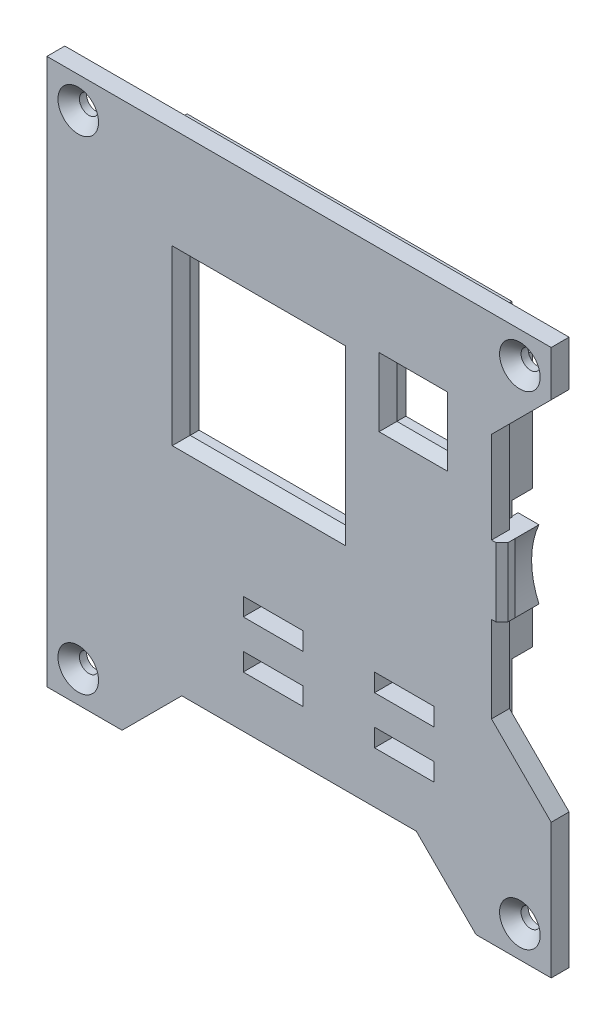
SolidWorks part; units mm, degrees
ref_plane "Front Plane" through (0, 0, 0) normal (0, 0, 1) x (1, 0, 0)
ref_plane "Top Plane" through (0, 0, 0) normal (0, 1, 0) x (1, 0, 0)
ref_plane "Right Plane" through (0, 0, 0) normal (1, 0, 0) x (0, 0, -1)
sketch "Sketch1" plane through (0, 0, 0) normal (0, 0, 1) x (1, 0, 0)
  line L0 (0.0172, 91.4623) -> (84.5172, 91.4623)
  line L1 (84.5172, 91.4623) -> (84.5172, 83.8623)
  line L2 (84.5172, 83.8623) -> (74.5172, 73.8623)
  line L3 (74.5172, 73.8623) -> (74.5172, 32.5623)
  line L4 (74.5172, 32.5623) -> (84.5172, 22.5623)
  line L5 (84.5172, 22.5623) -> (84.5172, -0.0377)
  line L6 (84.5172, -0.0377) -> (71.9172, -0.0377)
  line L7 (71.9172, -0.0377) -> (61.9172, 9.9623)
  line L8 (61.9172, 9.9623) -> (22.6172, 9.9623)
  line L9 (22.6172, 9.9623) -> (12.6172, -0.0377)
  line L10 (12.6172, -0.0377) -> (0.0172, -0.0377)
  line L11 (0.0172, -0.0377) -> (0.0172, 91.4623)
  dimension "D1" = 91.5
  dimension "D2" = 84.5
  dimension "D3" = 7.6
  dimension "D4" = 22.6
  dimension "D5" = 12.6
  dimension "D6" = 12.6
  dimension "D7" = 135
  dimension "D8" = 10
  dimension "D9" = 10
  dimension "D10" = 84.5
  dimension "D11" = 91.5
extrude "Boss-Extrude1" add sketch "Sketch1" along normal blind 3
sketch "Sketch3" plane through (0, 0, 3) normal (0, 0, 1) x (1, 0, 0)
  line L0 (84.5172, 91.4623) -> (0.0172, 91.4623) construction
  line L1 (5.2672, 86.2123) -> (79.2672, 86.2123) construction
  line L2 (5.2672, 86.2123) -> (5.2672, 5.2123) construction
  line L3 (5.2672, 5.2123) -> (79.2672, 5.2123) construction
  line L4 (79.2672, 86.2123) -> (79.2672, 5.2123) construction
  line L5 (5.2672, 86.2123) -> (79.2672, 5.2123) construction
  line L6 (5.2672, 5.2123) -> (79.2672, 86.2123) construction
  line L7 (0.0172, 91.4623) -> (0.0172, -0.0377) construction
  circle A0 centre (5.2672, 86.2123) radius 1.6
  circle A1 centre (79.2672, 86.2123) radius 1.6
  circle A2 centre (5.2672, 5.2123) radius 1.6
  circle A3 centre (79.2672, 5.2123) radius 1.6
  point P4 (42.2672, 45.7123)
  point P7 (42.2672, 91.4623)
  point P8 (42.2672, 86.2123)
  point P11 (0.0172, 45.7123)
  point P12 (5.2672, 45.7123)
  dimension "D3" = 3.2
  dimension "D4" = 3.2
  dimension "D5" = 3.2
  dimension "D6" = 3.2
  dimension "D1" = 74
  dimension "D2" = 81
extrude "Cut-Extrude1" cut sketch "Sketch3" against normal blind 3
chamfer "Chamfer1" distance 1.8 angle 45 4 edges at (6.8672, 5.2123, 3) (80.8672, 5.2123, 3) (80.8672, 86.2123, 3) (6.8672, 86.2123, 3)
sketch "Sketch5" plane through (0, 0, 3) normal (0, 0, 1) x (1, 0, 0)
  line L1 (22.5172, 72.9623) -> (48.5172, 72.9623)
  line L2 (22.5172, 72.9623) -> (22.5172, 46.9623)
  line L3 (22.5172, 46.9623) -> (48.5172, 46.9623)
  line L4 (48.5172, 72.9623) -> (48.5172, 46.9623)
  line L5 (57.1672, 74.8123) -> (65.6672, 74.8123)
  line L6 (57.1672, 74.8123) -> (57.1672, 66.3123)
  line L7 (57.1672, 66.3123) -> (65.6672, 66.3123)
  line L8 (65.6672, 74.8123) -> (65.6672, 66.3123)
  line L11 (84.5172, 91.4623) -> (0.0172, 91.4623) construction
  line L12 (0.0172, 91.4623) -> (0.0172, -0.0377) construction
  point P4 (29.4474, 52.8079)
  point P9 (65.6672, 70.5623)
  point P12 (61.4172, 74.8123)
  point P15 (35.5172, 72.9623)
  point P16 (22.5172, 59.9623)
  dimension "D1" = 8.5
  dimension "D2" = 8.5
  dimension "D3" = 26
  dimension "D4" = 26
  dimension "D5" = 20.9
  dimension "D6" = 61.4
  dimension "D7" = 35.5
  dimension "D8" = 31.5
extrude "Cut-Extrude2" cut sketch "Sketch5" against normal blind 3
chamfer "Chamfer2" distance 1.5 angle 45 8 edges at (48.5172, 59.9623, 3) (35.5172, 72.9623, 3) (22.5172, 59.9623, 3) (35.5172, 46.9623, 3) (61.4172, 66.3123, 3) (57.1672, 70.5623, 3) (61.4172, 74.8123, 3) (65.6672, 70.5623, 3)
sketch "Sketch7" plane through (0, 0, 3) normal (0, 0, 1) x (1, 0, 0)
  line L1 (72.7672, 58.5123) -> (76.2672, 58.5123)
  line L2 (72.7672, 58.5123) -> (72.7672, 47.0123)
  line L3 (72.7672, 47.0123) -> (76.2672, 47.0123)
  line L4 (76.2672, 58.5123) -> (76.2672, 47.0123)
  line L7 (74.5172, 32.5623) -> (74.5172, 73.8623) construction
  line L8 (84.5172, 91.4623) -> (0.0172, 91.4623) construction
  point P4 (76.2672, 52.7623)
  point P6 (74.5172, 58.5123)
  dimension "D1" = 38.7
  dimension "D2" = 11.5
  dimension "D3" = 3.5
extrude "Boss-Extrude3" add sketch "Sketch7" against normal blind 6.2
sketch "Sketch8" plane through (0, 0, -3.2) normal (0, 0, -1) x (-1, 0, 0)
  line L0 (-76.2672, 58.5123) -> (-76.2672, 47.0123)
  arc A0 (-76.2672, 58.5123) -> (-76.2672, 47.0123) centre (-89.0626, 52.7623) cw
extrude "Cut-Extrude3" cut sketch "Sketch8" against normal blind 3 and the other way through all
chamfer "Chamfer3" distance 1 angle 45 1 edges at (76.2672, 52.7623, -0.2)
sketch "Sketch9" plane through (0, 0, 0) normal (0, 0, -1) x (-1, 0, 0)
  line L0 (-48.5172, 46.9623) -> (-48.5172, 72.9623) construction
  line L1 (-48.0172, 39.9623) -> (-23.0172, 39.9623)
  line L2 (-48.0172, 39.9623) -> (-48.0172, 35.9623)
  line L3 (-48.0172, 35.9623) -> (-23.0172, 35.9623)
  line L4 (-23.0172, 39.9623) -> (-23.0172, 35.9623)
  line L5 (-46.5172, 74.9623) -> (-50.5172, 74.9623)
  line L6 (-46.5172, 74.9623) -> (-46.5172, 79.9623)
  line L7 (-46.5172, 79.9623) -> (-50.5172, 79.9623)
  line L8 (-50.5172, 74.9623) -> (-50.5172, 79.9623)
  line L9 (-24.5172, 74.9623) -> (-20.5172, 74.9623)
  line L10 (-24.5172, 74.9623) -> (-24.5172, 79.9623)
  line L11 (-24.5172, 79.9623) -> (-20.5172, 79.9623)
  line L12 (-20.5172, 74.9623) -> (-20.5172, 79.9623)
  line L13 (-22.5172, 72.9623) -> (-22.5172, 46.9623) construction
  line L14 (-48.5172, 72.9623) -> (-22.5172, 72.9623) construction
  line L15 (-22.5172, 46.9623) -> (-48.5172, 46.9623) construction
  dimension "D1" = 2
  dimension "D2" = 2
  dimension "D3" = 2
  dimension "D4" = 2
  dimension "D5" = 5
  dimension "D6" = 5
  dimension "D7" = 4
  dimension "D8" = 4
  dimension "D9" = 7
  dimension "D10" = 4
extrude "Boss-Extrude4" add sketch "Sketch9" along normal blind 1.9
sketch "Sketch10" plane through (0, 0, 0) normal (0, 0, -1) x (-1, 0, 0)
  line L0 (-84.5172, 91.4623) -> (-0.0172, 91.4623) construction
  line L1 (-21.4172, 80.9623) -> (-72.9172, 80.9623)
  line L2 (-21.4172, 80.9623) -> (-21.4172, 77.9623)
  line L3 (-21.4172, 77.9623) -> (-69.5172, 77.9623)
  line L6 (-72.9172, 80.9623) -> (-72.9172, 60.9623)
  line L7 (-72.9172, 60.9623) -> (-69.5172, 60.9623)
  line L8 (-69.5172, 77.9623) -> (-69.5172, 60.9623)
  line L9 (-72.9172, 44.4243) -> (-69.5172, 44.4243)
  line L10 (-72.9172, 44.4243) -> (-72.9172, 37.9623)
  line L12 (-69.5172, 44.4243) -> (-69.5172, 40.9623)
  line L13 (-52.9172, 37.9623) -> (-72.9172, 37.9623)
  line L14 (-52.9172, 37.9623) -> (-52.9172, 40.9623)
  line L15 (-52.9172, 40.9623) -> (-69.5172, 40.9623)
  line L17 (-74.5172, 58.5123) -> (-74.5172, 73.8623) construction
  line L18 (-74.5172, 32.5623) -> (-74.5172, 47.0123) construction
  line L19 (-22.6172, 9.9623) -> (-61.9172, 9.9623) construction
  point P8 (-72.5172, 86.0492)
  point P22 (-72.1549, 35.9623)
  dimension "D1" = 3
  dimension "D2" = 3.4
  dimension "D3" = 3.4
  dimension "D4" = 3
  dimension "D5" = 10.5
  dimension "D6" = 1.6
  dimension "D7" = 1.6
  dimension "D8" = 28
  dimension "D9" = 20
  dimension "D10" = 51.5
  dimension "D11" = 20
extrude "Boss-Extrude5" add sketch "Sketch10" along normal blind 5.5
sketch "Sketch11" plane through (0, 0, 0) normal (0, 0, -1) x (-1, 0, 0)
  line L0 (-0.0172, 91.4623) -> (-0.0172, -0.0377) construction
  line L1 (-24.0172, 36.4623) -> (-28.0172, 36.4623)
  line L2 (-24.0172, 36.4623) -> (-24.0172, 18.9623)
  line L3 (-24.0172, 18.9623) -> (-28.0172, 18.9623)
  line L4 (-28.0172, 36.4623) -> (-28.0172, 18.9623)
  line L5 (-22.6172, 9.9623) -> (-61.9172, 9.9623) construction
  dimension "D1" = 17.5
  dimension "D2" = 4
  dimension "D3" = 24
  dimension "D4" = 9
extrude "Boss-Extrude6" add sketch "Sketch11" along normal blind 3.5
sketch "Sketch12" plane through (0, 0, 0) normal (0, 0, -1) x (-1, 0, 0)
  line L0 (-0.0172, 91.4623) -> (-0.0172, -0.0377) construction
  line L1 (-19.7172, 79.9623) -> (-1.7172, 79.9623)
  line L2 (-19.7172, 79.9623) -> (-19.7172, 71.9623)
  line L3 (-19.7172, 71.9623) -> (-3.7172, 71.9623)
  line L4 (-1.7172, 79.9623) -> (-1.7172, 72.4623)
  line L5 (-19.7172, 11.4623) -> (-1.7172, 11.4623)
  line L6 (-19.7172, 11.4623) -> (-19.7172, 19.4623)
  line L7 (-19.7172, 19.4623) -> (-3.7172, 19.4623)
  line L8 (-1.7172, 11.4623) -> (-1.7172, 19.4623)
  line L9 (-84.5172, 91.4623) -> (-0.0172, 91.4623) construction
  line L10 (-0.0172, -0.0377) -> (-12.6172, -0.0377) construction
  line L13 (-1.7172, 72.4623) -> (-1.7172, 19.4623)
  line L15 (-3.7172, 71.9623) -> (-3.7172, 19.4623)
  dimension "D1" = 18
  dimension "D2" = 18
  dimension "D4" = 1.7
  dimension "D5" = 11.5
  dimension "D6" = 11.5
  dimension "D7" = 8
  dimension "D8" = 8
  dimension "D9" = 2
extrude "Boss-Extrude7" add sketch "Sketch12" along normal blind 4.5
sketch "Sketch13" plane through (0, 0, 0) normal (0, 0, -1) x (-1, 0, 0)
  line L1 (-18.5172, 77.9623) -> (-21.9172, 77.9623)
  line L4 (-21.9172, 77.9623) -> (-21.9172, 86.8623)
  line L5 (-21.4172, 80.9623) -> (-72.9172, 80.9623) construction
  line L7 (-18.5172, 89.8623) -> (-18.5172, 77.9623)
  line L8 (-21.9172, 86.8623) -> (-69.9172, 86.8623)
  line L10 (-72.9172, 89.8623) -> (-18.5172, 89.8623)
  line L11 (-72.9172, 89.8623) -> (-72.9172, 80.9623)
  line L12 (-72.9172, 80.9623) -> (-69.9172, 80.9623)
  line L13 (-69.9172, 86.8623) -> (-69.9172, 80.9623)
  line L14 (-72.9172, 37.9623) -> (-52.9172, 37.9623) construction
  line L15 (-72.9172, 37.9623) -> (-69.9172, 37.9623)
  line L16 (-72.9172, 37.9623) -> (-72.9172, 11.5623)
  line L17 (-72.9172, 11.5623) -> (-1.6172, 11.5623)
  line L18 (-69.9172, 37.9623) -> (-69.9172, 14.5623)
  line L19 (-72.9172, 37.9623) -> (-52.9172, 37.9623) construction
  line L20 (-0.0172, 91.4623) -> (-0.0172, -0.0377) construction
  line L22 (-1.6172, 11.5623) -> (-1.6172, 14.5623)
  line L23 (-1.6172, 14.5623) -> (-69.9172, 14.5623)
  line L25 (-69.5172, 60.9623) -> (-72.9172, 60.9623)
  line L26 (-69.5172, 60.9623) -> (-69.5172, 44.3758)
  line L27 (-69.5172, 44.3758) -> (-72.9172, 44.3758)
  line L28 (-72.9172, 60.9623) -> (-72.9172, 44.3758)
  line L29 (-84.5172, 91.4623) -> (-0.0172, 91.4623) construction
  line L30 (-74.5172, 58.5123) -> (-74.5172, 73.8623) construction
  line L32 (-22.6172, 9.9623) -> (-61.9172, 9.9623) construction
  line L33 (-74.5172, 32.5623) -> (-74.5172, 47.0123) construction
  point P35 (0, 0)
  point P37 (0, 0)
  dimension "D1" = 3
  dimension "D2" = 3
  dimension "D3" = 3
  dimension "D4" = 3
  dimension "D5" = 3.4
  dimension "D6" = 18.5
  dimension "D7" = 1.6
  dimension "D8" = 1.6
  dimension "D9" = 1.6
  dimension "D10" = 1.6
  dimension "D11" = 11.9
  dimension "D12" = 1.6
  dimension "D13" = 1.6
extrude "Boss-Extrude8" add sketch "Sketch13" along normal blind 2
sketch "Sketch14" plane through (0, 0, 0) normal (0, 0, -1) x (-1, 0, 0)
  line L5 (-32.9172, 21.5623) -> (-42.9172, 21.5623)
  line L6 (-32.9172, 21.5623) -> (-32.9172, 18.5623)
  line L7 (-32.9172, 18.5623) -> (-42.9172, 18.5623)
  line L8 (-42.9172, 21.5623) -> (-42.9172, 18.5623)
  line L9 (-54.9172, 21.5623) -> (-64.9172, 21.5623)
  line L10 (-54.9172, 21.5623) -> (-54.9172, 18.5623)
  line L11 (-54.9172, 18.5623) -> (-64.9172, 18.5623)
  line L12 (-64.9172, 21.5623) -> (-64.9172, 18.5623)
  line L14 (-19.7172, 14.5623) -> (-69.9172, 14.5623) construction
  line L15 (-69.9172, 14.5623) -> (-69.9172, 37.9623) construction
  line L16 (-32.9172, 29.5623) -> (-42.9172, 29.5623)
  line L17 (-32.9172, 29.5623) -> (-32.9172, 26.5623)
  line L18 (-32.9172, 26.5623) -> (-42.9172, 26.5623)
  line L19 (-42.9172, 29.5623) -> (-42.9172, 26.5623)
  line L20 (-54.9172, 29.5623) -> (-64.9172, 29.5623)
  line L21 (-54.9172, 29.5623) -> (-54.9172, 26.5623)
  line L22 (-54.9172, 26.5623) -> (-64.9172, 26.5623)
  line L23 (-64.9172, 29.5623) -> (-64.9172, 26.5623)
  point P12 (-54.9172, 20.0623)
  point P13 (-32.9172, 20.0623)
  point P25 (-54.9172, 28.0623)
  point P26 (-32.9172, 28.0623)
  point P27 (-59.9172, 26.5623)
  point P28 (-59.9172, 21.5623)
  point P29 (-37.9172, 26.5623)
  point P30 (-37.9172, 21.5623)
  point P31 (-42.9172, 28.0623)
  dimension "D1" = 10
  dimension "D2" = 10
  dimension "D3" = 4
  dimension "D4" = 3
  dimension "D5" = 3
  dimension "D6" = 5
  dimension "D7" = 12
  dimension "D8" = 10
  dimension "D9" = 10
  dimension "D10" = 3
  dimension "D11" = 5
  dimension "D12" = 3
extrude "Cut-Extrude4" cut sketch "Sketch14" against normal blind 3
chamfer "Chamfer4" distance 1 angle 45 1 edges at (76.2672, 52.7623, 3)
